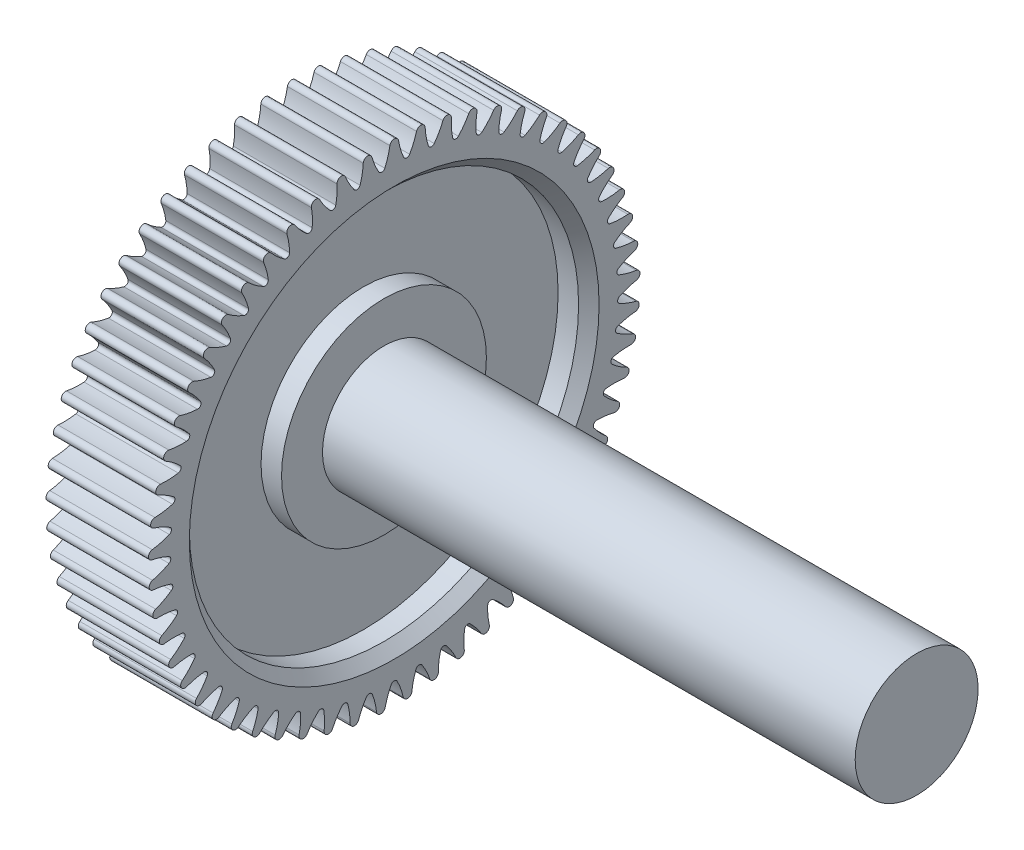
SolidWorks part; units mm, degrees
ref_plane "Front Plane" through (0, 0, 0) normal (0, 0, 1) x (1, 0, 0)
ref_plane "Top Plane" through (0, 0, 0) normal (0, 1, 0) x (1, 0, 0)
ref_plane "Right Plane" through (0, 0, 0) normal (1, 0, 0) x (0, 0, -1)
sketch "Sketch1" plane through (0, 0, 0) normal (0, 0, 1) x (1, 0, 0)
  line L0 (0, 0) -> (61, 0)
  line L1 (61, 0) -> (61, -6)
  line L2 (61, -6) -> (9, -6)
  line L3 (9, -6) -> (9, -10)
  line L4 (9, -10) -> (7, -10)
  line L5 (7, -10) -> (7, -19)
  line L6 (7, -19) -> (9, -19)
  line L7 (9, -19) -> (10, -20)
  line L8 (10, -20) -> (10, -24)
  line L9 (10, -24) -> (0, -24)
  line L10 (0, -24) -> (0, -20)
  line L11 (0, -20) -> (1, -19)
  line L12 (1, -19) -> (3, -19)
  line L13 (3, -19) -> (3, -10)
  line L14 (0, -6.127) -> (0, 0)
  arc A0 (3, -10) -> (0, -6.127) centre (-1, -10) ccw
  dimension "D8" = 4
  dimension "D1" = 6
  dimension "D2" = 61
  dimension "D3" = 52
  dimension "D4" = 1
  dimension "D5" = 2
  dimension "D6" = 10
  dimension "D7" = 4
  dimension "D9" = 2
  dimension "D10" = 5
  dimension "D11" = 4
  dimension "D12" = 10
  dimension "D13" = 19
revolve "Revolve1" add sketch "Sketch1" angle 360 about L0
sketch "Sketch3" plane through (10, 0, 0) normal (1, 0, 0) x (0, 0, -1)
  line L0 (0, 24) -> (0, 0) construction
  circle A0 centre (0, 0) radius 24 construction
  arc A1 (-0.4244, 23.6391) -> (0.4244, 23.6391) centre (0, 23.57) cw
  arc A2 (-0.4244, 23.6391) -> (-0.92, 21.9808) centre (-7.0669, 24.7209) cw
  arc A3 (3.0223, 23.449) -> (3.3325, 21.7461) centre (9.7435, 23.7935) ccw
  arc A4 (0.4244, 23.6391) -> (0.92, 21.9808) centre (7.0669, 24.7209) ccw
  circle A5 centre (0, 0) radius 22 construction
  arc A6 (2.1787, 23.5423) -> (1.5036, 21.9486) centre (-4.3045, 25.3483) cw
  arc A7 (2.1787, 23.5423) -> (3.0223, 23.449) centre (2.5929, 23.4269) cw
  arc A8 (5.5836, 22.9742) -> (5.7045, 21.2476) centre (12.3018, 22.5772) ccw
  arc A9 (4.7553, 23.1598) -> (3.909, 21.6499) centre (-1.4898, 25.668) cw
  arc A10 (4.7553, 23.1598) -> (5.5836, 22.9742) centre (5.1543, 22.9995) cw
  arc A11 (8.077, 22.2205) -> (8.0073, 20.4911) centre (14.7109, 21.0869) ccw
  arc A12 (7.2742, 22.4961) -> (6.267, 21.0885) centre (1.3429, 25.6761) cw
  arc A13 (7.2742, 22.4961) -> (8.077, 22.2205) centre (7.6532, 22.2929) cw
  arc A14 (10.4724, 21.1971) -> (10.2129, 19.4858) centre (16.9413, 19.3406) ccw
  arc A15 (9.7048, 21.5593) -> (8.5489, 20.2711) centre (4.1593, 25.3725) cw
  arc A16 (9.7048, 21.5593) -> (10.4724, 21.1971) centre (10.0591, 21.3157) cw
  arc A17 (12.7407, 19.9164) -> (12.2945, 18.2441) centre (18.9661, 17.3595) ccw
  arc A18 (12.0176, 20.3609) -> (10.727, 19.2076) centre (6.9253, 24.761) cw
  arc A19 (12.0176, 20.3609) -> (12.7407, 19.9164) centre (12.343, 20.0797) cw
  arc A20 (14.8544, 18.3939) -> (14.2269, 16.7808) centre (20.7607, 15.1677) ccw
  arc A21 (14.1845, 18.9153) -> (12.7749, 17.911) centre (9.6072, 23.8489) cw
  arc A22 (14.1845, 18.9153) -> (14.8544, 18.3939) centre (14.477, 18.6) cw
  arc A23 (16.7877, 16.6482) -> (15.9866, 15.1139) centre (22.3033, 12.7918) ccw
  arc A24 (16.1793, 17.24) -> (14.6677, 16.3969) centre (12.1724, 22.6473) cw
  arc A25 (16.1793, 17.24) -> (16.7877, 16.6482) centre (16.4353, 16.8946) cw
  arc A26 (18.5172, 14.7003) -> (17.5522, 13.2635) centre (23.5751, 10.2606) ccw
  arc A27 (17.9776, 15.3556) -> (16.3824, 14.6839) centre (14.5899, 21.1707) cw
  arc A28 (17.9776, 15.3556) -> (18.5172, 14.7003) centre (18.1941, 14.984) cw
  arc A29 (20.022, 12.5741) -> (18.9047, 11.2521) centre (24.5608, 7.6049) ccw
  arc A30 (19.5578, 13.2847) -> (17.8984, 12.7925) centre (16.8303, 19.4372) cw
  arc A31 (19.5578, 13.2847) -> (20.022, 12.5741) centre (19.732, 12.8916) cw
  arc A32 (21.2837, 10.2952) -> (20.0278, 9.1042) centre (25.2483, 4.8569) ccw
  arc A33 (20.9005, 11.0525) -> (19.197, 10.7459) centre (18.8664, 17.4678) cw
  arc A34 (20.9005, 11.0525) -> (21.2837, 10.2952) centre (21.0304, 10.6426) cw
  arc A35 (22.2871, 7.8913) -> (20.9078, 6.8457) centre (25.6294, 2.0499) ccw
  arc A36 (21.9895, 8.6862) -> (20.2626, 8.5689) centre (20.6735, 15.2863) cw
  arc A37 (21.9895, 8.6862) -> (22.2871, 7.8913) centre (22.0736, 8.2645) cw
  arc A38 (23.02, 5.3916) -> (21.534, 4.5041) centre (25.6993, -0.782) ccw
  arc A39 (22.8116, 6.2145) -> (21.0823, 6.2878) centre (22.2297, 12.9193) cw
  arc A40 (22.8116, 6.2145) -> (23.02, 5.3916) centre (22.8488, 5.7861) cw
  arc A41 (23.4734, 2.8265) -> (21.8988, 2.1079) centre (25.4573, -3.6044) ccw
  arc A42 (23.3568, 3.6673) -> (21.6461, 3.9304) centre (23.516, 10.3954) cw
  arc A43 (23.3568, 3.6673) -> (23.4734, 2.8265) centre (23.3466, 3.2374) cw
  arc A44 (23.6418, 0.2271) -> (21.9978, -0.314) centre (24.9063, -6.383) ccw
  arc A45 (23.6185, 1.0756) -> (21.9471, 1.5253) centre (24.5168, 7.7454) cw
  arc A46 (23.6185, 1.0756) -> (23.6418, 0.2271) centre (23.5611, 0.6495) cw
  arc A47 (23.5233, -2.3751) -> (21.8297, -2.732) centre (24.0529, -9.0842) ccw
  arc A48 (23.5934, -1.5291) -> (21.9817, -0.8983) centre (25.2201, 5.0013) cw
  arc A49 (23.5934, -1.5291) -> (23.5233, -2.3751) centre (23.4895, -1.9464) cw
  arc A50 (23.1193, -4.9484) -> (21.3967, -5.1169) centre (22.9076, -11.6751) ccw
  arc A51 (23.282, -4.1153) -> (21.7494, -3.311) centre (25.6172, 2.1965) cw
  arc A52 (23.282, -4.1153) -> (23.1193, -4.9484) centre (23.1328, -4.5186) cw
  arc A53 (22.4346, -7.4617) -> (20.7039, -7.4396) centre (21.4842, -14.1242) ccw
  arc A54 (22.688, -6.6516) -> (21.2532, -5.6835) centre (25.7034, -0.6349) cw
  arc A55 (22.688, -6.6516) -> (22.4346, -7.4617) centre (22.4953, -7.036) cw
  arc A56 (21.4776, -9.8844) -> (19.7598, -9.6721) centre (19.8, -16.402) ccw
  arc A57 (21.8186, -9.1071) -> (20.4989, -7.9871) centre (25.4775, -3.4586) cw
  arc A58 (21.8186, -9.1071) -> (21.4776, -9.8844) centre (21.5848, -9.468) cw
  arc A59 (20.2599, -12.1871) -> (18.5759, -11.7871) centre (17.8755, -18.4806) ccw
  arc A60 (20.6843, -11.452) -> (19.4959, -10.1936) centre (24.9424, -6.2404) cw
  arc A61 (20.6843, -11.452) -> (20.2599, -12.1871) centre (20.4122, -11.785) cw
  arc A62 (18.7962, -14.3419) -> (17.1665, -13.7591) centre (15.734, -20.3349) ccw
  arc A63 (19.2989, -13.6579) -> (18.2562, -12.2765) centre (24.1045, -8.9464) cw
  arc A64 (19.2989, -13.6579) -> (18.7962, -14.3419) centre (18.9919, -13.959) cw
  arc A65 (17.1044, -16.3226) -> (15.5487, -15.564) centre (13.4015, -21.9423) ccw
  arc A66 (17.6793, -15.6981) -> (16.7949, -14.2103) centre (22.9741, -11.5438) cw
  arc A67 (17.6793, -15.6981) -> (17.1044, -16.3226) centre (17.341, -15.9635) cw
  arc A68 (15.205, -18.1051) -> (13.7421, -17.18) centre (10.9063, -23.2834) ccw
  arc A69 (15.8451, -17.5477) -> (15.1297, -15.9716) centre (21.5647, -14.001) cw
  arc A70 (15.8451, -17.5477) -> (15.205, -18.1051) centre (15.4796, -17.7743) cw
  arc A71 (13.121, -19.6679) -> (11.7688, -18.5875) centre (8.2788, -24.3419) ccw
  arc A72 (13.8185, -19.1843) -> (13.2808, -17.5391) centre (19.8936, -16.2884) cw
  arc A73 (13.8185, -19.1843) -> (13.121, -19.6679) centre (13.4304, -19.3693) cw
  arc A74 (10.8777, -20.992) -> (9.6526, -19.7694) centre (5.5507, -25.1049) ccw
  arc A75 (11.6242, -20.588) -> (11.2708, -18.8936) centre (17.981, -18.378) cw
  arc A76 (11.6242, -20.588) -> (10.8777, -20.992) centre (11.2181, -20.7292) cw
  arc A77 (8.5024, -22.0612) -> (7.4192, -20.7112) centre (2.7553, -25.5631) ccw
  arc A78 (9.2888, -21.7418) -> (9.1239, -20.0188) centre (15.8502, -20.2445) cw
  arc A79 (9.2888, -21.7418) -> (8.5024, -22.0612) centre (8.8696, -21.8375) cw
  arc A80 (6.0239, -22.8627) -> (5.0958, -21.4017) centre (-0.0736, -25.7111) ccw
  arc A81 (6.8407, -22.6317) -> (6.8663, -20.901) centre (13.5269, -21.8653) cw
  arc A82 (6.8407, -22.6317) -> (6.0239, -22.8627) centre (6.4135, -22.6807) cw
  arc A83 (3.4723, -23.3866) -> (2.7105, -21.8324) centre (-2.9016, -25.547) ccw
  arc A84 (4.3095, -23.2469) -> (4.5254, -21.5295) centre (11.0394, -23.2206) cw
  arc A85 (4.3095, -23.2469) -> (3.4723, -23.3866) centre (3.8795, -23.2485) cw
  arc A86 (0.8785, -23.6266) -> (0.2923, -21.9981) centre (-5.6943, -25.0727) ccw
  arc A87 (1.726, -23.5798) -> (2.1295, -21.8967) centre (8.418, -24.2941) cw
  arc A88 (1.726, -23.5798) -> (0.8785, -23.6266) centre (1.2984, -23.5342) cw
  arc A89 (-1.726, -23.5798) -> (-2.1295, -21.8967) centre (-8.418, -24.2941) ccw
  arc A90 (-0.8785, -23.6266) -> (-0.2923, -21.9981) centre (5.6943, -25.0727) cw
  arc A91 (-0.8785, -23.6266) -> (-1.726, -23.5798) centre (-1.2984, -23.5342) cw
  arc A92 (-4.3095, -23.2469) -> (-4.5254, -21.5295) centre (-11.0394, -23.2206) ccw
  arc A93 (-3.4723, -23.3866) -> (-2.7105, -21.8324) centre (2.9016, -25.547) cw
  arc A94 (-3.4723, -23.3866) -> (-4.3095, -23.2469) centre (-3.8795, -23.2485) cw
  arc A95 (-6.8407, -22.6317) -> (-6.8663, -20.901) centre (-13.5269, -21.8653) ccw
  arc A96 (-6.0239, -22.8627) -> (-5.0958, -21.4017) centre (0.0736, -25.7111) cw
  arc A97 (-6.0239, -22.8627) -> (-6.8407, -22.6317) centre (-6.4135, -22.6807) cw
  arc A98 (-9.2888, -21.7418) -> (-9.1239, -20.0188) centre (-15.8502, -20.2445) ccw
  arc A99 (-8.5024, -22.0612) -> (-7.4192, -20.7112) centre (-2.7553, -25.5631) cw
  arc A100 (-8.5024, -22.0612) -> (-9.2888, -21.7418) centre (-8.8696, -21.8375) cw
  arc A101 (-11.6242, -20.588) -> (-11.2708, -18.8936) centre (-17.981, -18.378) ccw
  arc A102 (-10.8777, -20.992) -> (-9.6526, -19.7694) centre (-5.5507, -25.1049) cw
  arc A103 (-10.8777, -20.992) -> (-11.6242, -20.588) centre (-11.2181, -20.7292) cw
  arc A104 (-13.8185, -19.1843) -> (-13.2808, -17.5391) centre (-19.8936, -16.2884) ccw
  arc A105 (-13.121, -19.6679) -> (-11.7688, -18.5875) centre (-8.2788, -24.3419) cw
  arc A106 (-13.121, -19.6679) -> (-13.8185, -19.1843) centre (-13.4304, -19.3693) cw
  arc A107 (-15.8451, -17.5477) -> (-15.1297, -15.9716) centre (-21.5647, -14.001) ccw
  arc A108 (-15.205, -18.1051) -> (-13.7421, -17.18) centre (-10.9063, -23.2834) cw
  arc A109 (-15.205, -18.1051) -> (-15.8451, -17.5477) centre (-15.4796, -17.7743) cw
  arc A110 (-17.6793, -15.6981) -> (-16.7949, -14.2103) centre (-22.9741, -11.5438) ccw
  arc A111 (-17.1044, -16.3226) -> (-15.5487, -15.564) centre (-13.4015, -21.9423) cw
  arc A112 (-17.1044, -16.3226) -> (-17.6793, -15.6981) centre (-17.341, -15.9635) cw
  arc A113 (-19.2989, -13.6579) -> (-18.2562, -12.2765) centre (-24.1045, -8.9464) ccw
  arc A114 (-18.7962, -14.3419) -> (-17.1665, -13.7591) centre (-15.734, -20.3349) cw
  arc A115 (-18.7962, -14.3419) -> (-19.2989, -13.6579) centre (-18.9919, -13.959) cw
  arc A116 (-20.6843, -11.452) -> (-19.4959, -10.1936) centre (-24.9424, -6.2404) ccw
  arc A117 (-20.2599, -12.1871) -> (-18.5759, -11.7871) centre (-17.8755, -18.4806) cw
  arc A118 (-20.2599, -12.1871) -> (-20.6843, -11.452) centre (-20.4122, -11.785) cw
  arc A119 (-21.8186, -9.1071) -> (-20.4989, -7.9871) centre (-25.4775, -3.4586) ccw
  arc A120 (-21.4776, -9.8844) -> (-19.7598, -9.6721) centre (-19.8, -16.402) cw
  arc A121 (-21.4776, -9.8844) -> (-21.8186, -9.1071) centre (-21.5848, -9.468) cw
  arc A122 (-22.688, -6.6516) -> (-21.2532, -5.6835) centre (-25.7034, -0.6349) ccw
  arc A123 (-22.4346, -7.4617) -> (-20.7039, -7.4396) centre (-21.4842, -14.1242) cw
  arc A124 (-22.4346, -7.4617) -> (-22.688, -6.6516) centre (-22.4953, -7.036) cw
  arc A125 (-23.282, -4.1153) -> (-21.7494, -3.311) centre (-25.6172, 2.1965) ccw
  arc A126 (-23.1193, -4.9484) -> (-21.3967, -5.1169) centre (-22.9076, -11.6751) cw
  arc A127 (-23.1193, -4.9484) -> (-23.282, -4.1153) centre (-23.1328, -4.5186) cw
  arc A128 (-23.5934, -1.5291) -> (-21.9817, -0.8983) centre (-25.2201, 5.0013) ccw
  arc A129 (-23.5233, -2.3751) -> (-21.8297, -2.732) centre (-24.0529, -9.0842) cw
  arc A130 (-23.5233, -2.3751) -> (-23.5934, -1.5291) centre (-23.4895, -1.9464) cw
  arc A131 (-23.6185, 1.0756) -> (-21.9471, 1.5253) centre (-24.5168, 7.7454) ccw
  arc A132 (-23.6418, 0.2271) -> (-21.9978, -0.314) centre (-24.9063, -6.383) cw
  arc A133 (-23.6418, 0.2271) -> (-23.6185, 1.0756) centre (-23.5611, 0.6495) cw
  arc A134 (-23.3568, 3.6673) -> (-21.6461, 3.9304) centre (-23.516, 10.3954) ccw
  arc A135 (-23.4734, 2.8265) -> (-21.8988, 2.1079) centre (-25.4573, -3.6044) cw
  arc A136 (-23.4734, 2.8265) -> (-23.3568, 3.6673) centre (-23.3466, 3.2374) cw
  arc A137 (-22.8116, 6.2145) -> (-21.0823, 6.2878) centre (-22.2297, 12.9193) ccw
  arc A138 (-23.02, 5.3916) -> (-21.534, 4.5041) centre (-25.6993, -0.782) cw
  arc A139 (-23.02, 5.3916) -> (-22.8116, 6.2145) centre (-22.8488, 5.7861) cw
  arc A140 (-21.9895, 8.6862) -> (-20.2626, 8.5689) centre (-20.6735, 15.2863) ccw
  arc A141 (-22.2871, 7.8913) -> (-20.9078, 6.8457) centre (-25.6294, 2.0499) cw
  arc A142 (-22.2871, 7.8913) -> (-21.9895, 8.6862) centre (-22.0736, 8.2645) cw
  arc A143 (-20.9005, 11.0525) -> (-19.197, 10.7459) centre (-18.8664, 17.4678) ccw
  arc A144 (-21.2837, 10.2952) -> (-20.0278, 9.1042) centre (-25.2483, 4.8569) cw
  arc A145 (-21.2837, 10.2952) -> (-20.9005, 11.0525) centre (-21.0304, 10.6426) cw
  arc A146 (-19.5578, 13.2847) -> (-17.8984, 12.7925) centre (-16.8303, 19.4372) ccw
  arc A147 (-20.022, 12.5741) -> (-18.9047, 11.2521) centre (-24.5608, 7.6049) cw
  arc A148 (-20.022, 12.5741) -> (-19.5578, 13.2847) centre (-19.732, 12.8916) cw
  arc A149 (-17.9776, 15.3556) -> (-16.3824, 14.6839) centre (-14.5899, 21.1707) ccw
  arc A150 (-18.5172, 14.7003) -> (-17.5522, 13.2635) centre (-23.5751, 10.2606) cw
  arc A151 (-18.5172, 14.7003) -> (-17.9776, 15.3556) centre (-18.1941, 14.984) cw
  arc A152 (-16.1793, 17.24) -> (-14.6677, 16.3969) centre (-12.1724, 22.6473) ccw
  arc A153 (-16.7877, 16.6482) -> (-15.9866, 15.1139) centre (-22.3033, 12.7918) cw
  arc A154 (-16.7877, 16.6482) -> (-16.1793, 17.24) centre (-16.4353, 16.8946) cw
  arc A155 (-14.1845, 18.9153) -> (-12.7749, 17.911) centre (-9.6072, 23.8489) ccw
  arc A156 (-14.8544, 18.3939) -> (-14.2269, 16.7808) centre (-20.7607, 15.1677) cw
  arc A157 (-14.8544, 18.3939) -> (-14.1845, 18.9153) centre (-14.477, 18.6) cw
  arc A158 (-12.0176, 20.3609) -> (-10.727, 19.2076) centre (-6.9253, 24.761) ccw
  arc A159 (-12.7407, 19.9164) -> (-12.2945, 18.2441) centre (-18.9661, 17.3595) cw
  arc A160 (-12.7407, 19.9164) -> (-12.0176, 20.3609) centre (-12.343, 20.0797) cw
  arc A161 (-9.7048, 21.5593) -> (-8.5489, 20.2711) centre (-4.1593, 25.3725) ccw
  arc A162 (-10.4724, 21.1971) -> (-10.2129, 19.4858) centre (-16.9413, 19.3406) cw
  arc A163 (-10.4724, 21.1971) -> (-9.7048, 21.5593) centre (-10.0591, 21.3157) cw
  arc A164 (-7.2742, 22.4961) -> (-6.267, 21.0885) centre (-1.3429, 25.6761) ccw
  arc A165 (-8.077, 22.2205) -> (-8.0073, 20.4911) centre (-14.7109, 21.0869) cw
  arc A166 (-8.077, 22.2205) -> (-7.2742, 22.4961) centre (-7.6532, 22.2929) cw
  arc A167 (-4.7553, 23.1598) -> (-3.909, 21.6499) centre (1.4898, 25.668) ccw
  arc A168 (-5.5836, 22.9742) -> (-5.7045, 21.2476) centre (-12.3018, 22.5772) cw
  arc A169 (-5.5836, 22.9742) -> (-4.7553, 23.1598) centre (-5.1543, 22.9995) cw
  arc A170 (-2.1787, 23.5423) -> (-1.5036, 21.9486) centre (4.3045, 25.3483) ccw
  arc A171 (-3.0223, 23.449) -> (-3.3325, 21.7461) centre (-9.7435, 23.7935) cw
  arc A172 (-3.0223, 23.449) -> (-2.1787, 23.5423) centre (-2.5929, 23.4269) cw
  arc A173 (0.92, 21.9808) -> (1.5036, 21.9486) centre (1.2201, 22.1145) ccw
  arc A174 (3.3325, 21.7461) -> (3.909, 21.6499) centre (3.6455, 21.8461) ccw
  arc A175 (5.7045, 21.2476) -> (6.267, 21.0885) centre (6.0266, 21.3125) ccw
  arc A176 (8.0073, 20.4911) -> (8.5489, 20.2711) centre (8.3346, 20.5201) ccw
  arc A177 (10.2129, 19.4858) -> (10.727, 19.2076) centre (10.5414, 19.4787) ccw
  arc A178 (12.2945, 18.2441) -> (12.7749, 17.911) centre (12.6202, 18.2009) ccw
  arc A179 (14.2269, 16.7808) -> (14.6677, 16.3969) centre (14.5459, 16.7021) ccw
  arc A180 (15.9866, 15.1139) -> (16.3824, 14.6839) centre (16.2949, 15.0005) ccw
  arc A181 (17.5522, 13.2635) -> (17.8984, 12.7925) centre (17.8462, 13.1169) ccw
  arc A182 (18.9047, 11.2521) -> (19.197, 10.7459) centre (19.1809, 11.0741) ccw
  arc A183 (20.0278, 9.1042) -> (20.2626, 8.5689) centre (20.2827, 8.8968) ccw
  arc A184 (20.9078, 6.8457) -> (21.0823, 6.2878) centre (21.1383, 6.6116) ccw
  arc A185 (21.534, 4.5041) -> (21.6461, 3.9304) centre (21.7373, 4.246) ccw
  arc A186 (21.8988, 2.1079) -> (21.9471, 1.5253) centre (22.0725, 1.829) ccw
  arc A187 (21.9978, -0.314) -> (21.9817, -0.8983) centre (22.1398, -0.6103) ccw
  arc A188 (21.8297, -2.732) -> (21.7494, -3.311) centre (21.9382, -3.0421) ccw
  arc A189 (21.3967, -5.1169) -> (21.2532, -5.6835) centre (21.4704, -5.4371) ccw
  arc A190 (20.7039, -7.4396) -> (20.4989, -7.9871) centre (20.742, -7.766) ccw
  arc A191 (19.7598, -9.6721) -> (19.4959, -10.1936) centre (19.7618, -10.0006) ccw
  arc A192 (18.5759, -11.7871) -> (18.2562, -12.2765) centre (18.5417, -12.1139) ccw
  arc A193 (17.1665, -13.7591) -> (16.7949, -14.2103) centre (17.0965, -14.0801) ccw
  arc A194 (15.5487, -15.564) -> (15.1297, -15.9716) centre (15.4438, -15.8754) ccw
  arc A195 (13.7421, -17.18) -> (13.2808, -17.5391) centre (13.6037, -17.478) ccw
  arc A196 (11.7688, -18.5875) -> (11.2708, -18.8936) centre (11.5984, -18.8685) ccw
  arc A197 (9.6526, -19.7694) -> (9.1239, -20.0188) centre (9.4523, -20.0299) ccw
  arc A198 (7.4192, -20.7112) -> (6.8663, -20.901) centre (7.1915, -20.9481) ccw
  arc A199 (5.0958, -21.4017) -> (4.5254, -21.5295) centre (4.8434, -21.6121) ccw
  arc A200 (2.7105, -21.8324) -> (2.1295, -21.8967) centre (2.4365, -22.0137) ccw
  arc A201 (0.2923, -21.9981) -> (-0.2923, -21.9981) centre (0, -22.1482) ccw
  arc A202 (-2.1295, -21.8967) -> (-2.7105, -21.8324) centre (-2.4365, -22.0137) ccw
  arc A203 (-4.5254, -21.5295) -> (-5.0958, -21.4017) centre (-4.8434, -21.6121) ccw
  arc A204 (-6.8663, -20.901) -> (-7.4192, -20.7112) centre (-7.1915, -20.9481) ccw
  arc A205 (-9.1239, -20.0188) -> (-9.6526, -19.7694) centre (-9.4523, -20.0299) ccw
  arc A206 (-11.2708, -18.8936) -> (-11.7688, -18.5875) centre (-11.5984, -18.8685) ccw
  arc A207 (-13.2808, -17.5391) -> (-13.7421, -17.18) centre (-13.6037, -17.478) ccw
  arc A208 (-15.1297, -15.9716) -> (-15.5487, -15.564) centre (-15.4438, -15.8754) ccw
  arc A209 (-16.7949, -14.2103) -> (-17.1665, -13.7591) centre (-17.0965, -14.0801) ccw
  arc A210 (-18.2562, -12.2765) -> (-18.5759, -11.7871) centre (-18.5417, -12.1139) ccw
  arc A211 (-19.4959, -10.1936) -> (-19.7598, -9.6721) centre (-19.7618, -10.0006) ccw
  arc A212 (-20.4989, -7.9871) -> (-20.7039, -7.4396) centre (-20.742, -7.766) ccw
  arc A213 (-21.2532, -5.6835) -> (-21.3967, -5.1169) centre (-21.4704, -5.4371) ccw
  arc A214 (-21.7494, -3.311) -> (-21.8297, -2.732) centre (-21.9382, -3.0421) ccw
  arc A215 (-21.9817, -0.8983) -> (-21.9978, -0.314) centre (-22.1398, -0.6103) ccw
  arc A216 (-21.9471, 1.5253) -> (-21.8988, 2.1079) centre (-22.0725, 1.829) ccw
  arc A217 (-21.6461, 3.9304) -> (-21.534, 4.5041) centre (-21.7373, 4.246) ccw
  arc A218 (-21.0823, 6.2878) -> (-20.9078, 6.8457) centre (-21.1383, 6.6116) ccw
  arc A219 (-20.2626, 8.5689) -> (-20.0278, 9.1042) centre (-20.2827, 8.8968) ccw
  arc A220 (-19.197, 10.7459) -> (-18.9047, 11.2521) centre (-19.1809, 11.0741) ccw
  arc A221 (-17.8984, 12.7925) -> (-17.5522, 13.2635) centre (-17.8462, 13.1169) ccw
  arc A222 (-16.3824, 14.6839) -> (-15.9866, 15.1139) centre (-16.2949, 15.0005) ccw
  arc A223 (-14.6677, 16.3969) -> (-14.2269, 16.7808) centre (-14.5459, 16.7021) ccw
  arc A224 (-12.7749, 17.911) -> (-12.2945, 18.2441) centre (-12.6202, 18.2009) ccw
  arc A225 (-10.727, 19.2076) -> (-10.2129, 19.4858) centre (-10.5414, 19.4787) ccw
  arc A226 (-8.5489, 20.2711) -> (-8.0073, 20.4911) centre (-8.3346, 20.5201) ccw
  arc A227 (-6.267, 21.0885) -> (-5.7045, 21.2476) centre (-6.0266, 21.3125) ccw
  arc A228 (-3.909, 21.6499) -> (-3.3325, 21.7461) centre (-3.6455, 21.8461) ccw
  arc A229 (-1.5036, 21.9486) -> (-0.92, 21.9808) centre (-1.2201, 22.1145) ccw
  circle A230 centre (0, 0) radius 24
  point P408 (0, 0)
  point P578 (0, 0)
  circle M232 centre (0, 0) radius 24
  dimension "D1" = 0.43
  dimension "D2" = 44
  dimension "D3" = 6.73
  dimension "D4" = 6.73
  dimension "D5" = 1.84
  dimension "D6" = 0.92
  dimension "D7" = 57
  dimension "D8" = 57
extrude "Cut-Extrude1" cut sketch "Sketch3" against normal blind 10 contours A134 A217 A138 A139 A136 M232 | A131 A216 A135 A136 A133 M232 | A128 A215 A132 A133 A130 M232 | A125 A214 A129 A130 A127 M232 | A122 A213 A126 A127 A124 M232 | A119 A212 A123 A124 A121 M232 | A116 A211 A120 A121 A118 M232 | A113 A210 A117 A118 A115 M232 | A110 A209 A114 A115 A112 M232 | A107 A208 A111 A112 A109 M232 | A170 A229 A2 A1 A172 M232 | A4 A173 A6 A7 A1 M232 | A3 A174 A9 A10 A7 M232 | A8 A175 A12 A13 A10 M232 | A11 A176 A15 A16 A13 M232 | A14 A177 A18 A19 A16 M232 | A17 A178 A21 A22 A19 M232 | A167 A228 A171 A172 A169 M232 | A164 A227 A168 A169 A166 M232 | A161 A226 A165 A166 A163 M232 | A158 A225 A162 A163 A160 M232 | A20 A179 A24 A25 A22 M232 | A23 A180 A27 A28 A25 M232 | A26 A181 A30 A31 A28 M232 | A29 A182 A33 A34 A31 M232 | A32 A183 A36 A37 A34 M232 | A35 A184 A39 A40 A37 M232 | A38 A185 A42 A43 A40 M232 | A41 A186 A45 A46 A43 M232 | A44 A187 A48 A49 A46 M232 | A47 A188 A51 A52 A49 M232 | A50 A189 A54 A55 A52 M232 | A53 A190 A57 A58 A55 M232 | A56 A191 A60 A61 A58 M232 | A59 A192 A63 A64 A61 M232 | A62 A193 A66 A67 A64 M232 | A65 A194 A69 A70 A67 M232 | A68 A195 A72 A73 A70 M232 | A71 A196 A75 A76 A73 M232 | A74 A197 A78 A79 A76 M232 | A77 A198 A81 A82 A79 M232 | A80 A199 A84 A85 A82 M232 | A83 A200 A87 A88 A85 M232 | A86 A201 A90 A91 A88 M232 | A89 A202 A93 A94 A91 M232 | A92 A203 A96 A97 A94 M232 | A95 A204 A99 A100 A97 M232 | A98 A205 A102 A103 A100 M232 | A101 A206 A105 A106 A103 M232 | A104 A207 A108 A109 A106 M232 | A155 A224 A159 A160 A157 M232 | A152 A223 A156 A157 A154 M232 | A149 A222 A153 A154 A151 M232 | A146 A221 A150 A151 A148 M232 | A143 A220 A147 A148 A145 M232 | A140 A219 A144 A145 A142 M232 | A137 A218 A141 A142 A139 M232 region at (10, 23.1031, 1.2746) region at (10, 23.1031, -1.2746) region at (10, 22.8226, -3.8084) region at (10, 22.8226, 3.8084) region at (10, 22.2651, -6.296) region at (10, 22.2651, 6.296) region at (10, 21.4374, -8.7071) region at (10, 21.4374, 8.7071) region at (10, 20.3494, -11.0126) region at (10, 20.3494, 11.0126) region at (10, 19.0144, -13.1843) region at (10, 19.0144, 13.1843) region at (10, 17.4487, -15.1961) region at (10, 17.4487, 15.1961) region at (10, 15.6711, -17.0233) region at (10, 15.6711, 17.0233) region at (10, 13.7032, -18.6439) region at (10, 13.7032, 18.6439) region at (10, 11.5691, -20.0383) region at (10, 11.5691, 20.0383) region at (10, 9.2945, -21.1893) region at (10, 9.2945, 21.1893) region at (10, 6.9071, -22.0832) region at (10, 6.9071, 22.0832) region at (10, 4.4358, -22.709) region at (10, 4.4358, 22.709) region at (10, 1.9107, -23.0592) region at (10, 1.9107, 23.0592) region at (10, -0.6376, -23.1294) region at (10, -0.6376, 23.1294) region at (10, -3.1781, 22.9189) region at (10, -3.1781, -22.9189) region at (10, -5.6801, 22.4302) region at (10, -5.6801, -22.4302) region at (10, -8.1131, 21.6692) region at (10, -8.1131, -21.6692) region at (10, -10.4477, 20.6451) region at (10, -10.4477, -20.6451) region at (10, -12.6554, 19.3705) region at (10, -12.6554, -19.3705) region at (10, -14.7095, 17.8608) region at (10, -14.7095, -17.8608) region at (10, -16.585, 16.1342) region at (10, -16.585, -16.1342) region at (10, -18.2593, 14.2118) region at (10, -18.2593, -14.2118) region at (10, -19.7119, 12.1168) region at (10, -19.7119, -12.1168) region at (10, -20.9252, 9.8748) region at (10, -20.9252, -9.8748) region at (10, -21.8845, 7.513) region at (10, -21.8845, -7.513) region at (10, -22.5782, 5.0599) region at (10, -22.5782, -5.0599) region at (10, -22.9978, 2.5454) region at (10, -22.9978, -2.5454) region at (10, -23.1382, 0)
